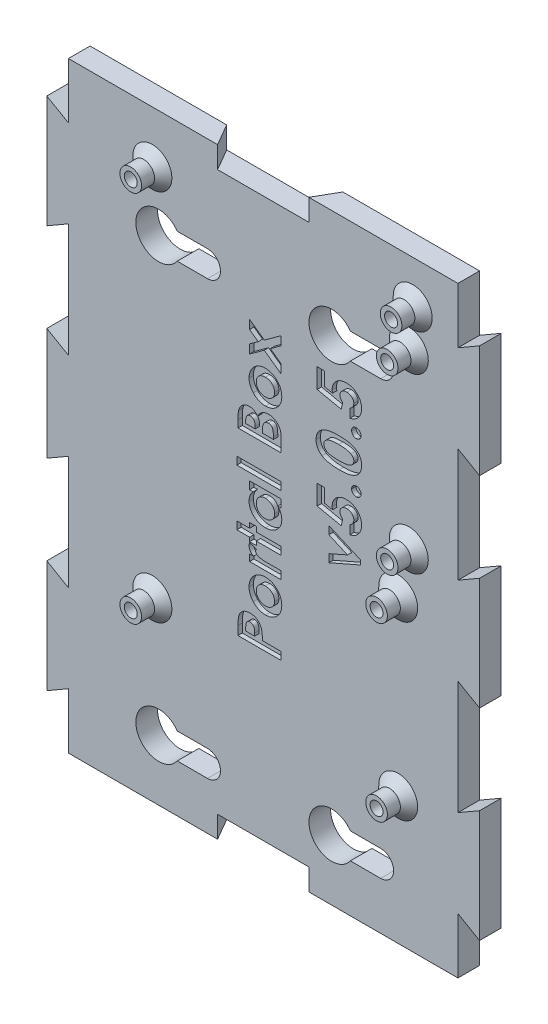
SolidWorks part; units mm, degrees
ref_plane "Front Plane" through (0, 0, 0) normal (1, 0, 0) x (0, 1, 0)
ref_plane "Top Plane" through (0, 0, 0) normal (0, 0, 1) x (0, 1, 0)
ref_plane "Right Plane" through (0, 0, 0) normal (0, 1, 0) x (-1, 0, 0)
sketch "Sketch2" plane through (0, 0, 0) normal (0, 0, 1) x (0, 1, 0)
  line L1 (-60.1282, -37.9423) -> (59.8718, -37.9423) construction
  line L2 (-60.1282, -37.9423) -> (-60.1282, 42.0577) construction
  line L3 (-60.1282, 42.0577) -> (59.8718, 42.0577) construction
  line L4 (59.8718, -37.9423) -> (59.8718, 42.0577) construction
  line L13 (-72.6282, 49.5577) -> (66.3718, 49.5577)
  line L14 (-72.6282, 49.5577) -> (-72.6282, -40.4423)
  line L15 (-72.6282, -40.4423) -> (66.3718, -40.4423)
  line L16 (66.3718, 49.5577) -> (66.3718, -40.4423)
  point P0 (0, 0)
  point P6 (0, 0)
  dimension "D1" = 120
  dimension "D2" = 80
  dimension "D3" = 12.5
  dimension "D5" = 139
  dimension "D6" = 90
  dimension "D7" = 7.5
extrude "Boss-Extrude1" add sketch "Sketch2" along normal blind 5
sketch "Sketch9" plane through (0, 0, 5) normal (0, 0, 1) x (1, 0, 0)
  line L0 (-0.3883, 34.4618) -> (-0.3883, -36.7916) construction
  text T0 "<b>Portal Box</b>\r\n<b> v5.0.5</b>" font "Century Gothic" height 10
extrude "Cut-Extrude4" cut sketch "Sketch9" against normal blind 1
sketch "Sketch12" plane through (0, 0, 5) normal (0, 0, 1) x (1, 0, 0)
  line L0 (-54.5577, 30.3911) -> (-54.5577, 56.3718)
  line L1 (-54.5577, 56.3718) -> (-32.0577, 43.3815)
  line L2 (-32.0577, 43.3815) -> (-54.5577, 30.3911)
  line L4 (-32.0577, -3.1282) -> (-54.5577, -16.1185)
  line L5 (-54.5577, -16.1185) -> (-54.5577, 9.8622)
  line L6 (-54.5577, 9.8622) -> (-32.0577, -3.1282)
  line L7 (-32.0577, -49.6378) -> (-54.5577, -62.6282)
  line L8 (-54.5577, -62.6282) -> (-54.5577, -36.6474)
  line L9 (-54.5577, -36.6474) -> (-32.0577, -49.6378)
  line L11 (0, 70.08) -> (0, -71.8273) construction
  line L12 (0, -55) -> (0, 55) construction
  line L22 (-49.5577, 66.3718) -> (-49.5577, -72.6282) construction
  line L23 (40.4423, 66.3718) -> (-49.5577, 66.3718) construction
  line L24 (-49.5577, -72.6282) -> (40.4423, -72.6282) construction
  line L26 (-4.5577, 66.3718) -> (-4.5577, -72.6282) construction
  line L28 (45.4423, 56.3718) -> (22.9423, 43.3815)
  line L29 (45.4423, 30.3911) -> (45.4423, 56.3718)
  line L30 (22.9423, 43.3815) -> (45.4423, 30.3911)
  line L31 (45.4423, 9.8622) -> (22.9423, -3.1282)
  line L32 (45.4423, -16.1185) -> (45.4423, 9.8622)
  line L33 (22.9423, -3.1282) -> (45.4423, -16.1185)
  line L34 (45.4423, -36.6474) -> (22.9423, -49.6378)
  line L35 (45.4423, -62.6282) -> (45.4423, -36.6474)
  line L36 (22.9423, -49.6378) -> (45.4423, -62.6282)
  circle A0 centre (-47.0577, 43.3815) radius 7.5
  dimension "D1" = 15
  dimension "D2" = 5
  dimension "D4" = 10
  dimension "D5" = 10
  dimension "D9" = 20.5289
  dimension "D10" = 20.5289
  dimension "D3" = 3
extrude "Boss-Extrude5" add sketch "Sketch12" against normal blind 5 contours L9 L8 L7 | L6 L5 L4 | A0 L0 L2 | A0 | A0 L1 L0 | A0 L2 L1 | L34 | L31 | L28 L30 L29 region at (-51.7998, 35.168, 5) region at (-51.7998, 51.5949, 5) region at (-47.0577, 43.3815, 5) region at (-37.5737, 43.3815, 5) region at (-47.0577, -3.1282, 5) region at (-47.0577, -49.6378, 5) region at (37.9423, -3.1282, 5) region at (37.9423, -49.6378, 5)
sketch "Sketch13" plane through (0, 66.3718, -60) normal (0, 1, 0) x (1, 0, 0)
  line L0 (-17.9811, -60) -> (8.8657, -60)
  line L1 (8.8657, -60) -> (-4.5577, -83.25)
  line L2 (-4.5577, -83.25) -> (-17.9811, -60)
  line L5 (40.4423, -65) -> (40.4423, -60) construction
  line L6 (-55, -60) -> (55, -60) construction
  circle A0 centre (-4.5577, -67.75) radius 7.75
  dimension "D1" = 15.5
  dimension "D2" = 0
  dimension "D3" = 45
extrude "Cut-Extrude5" cut sketch "Sketch13" along normal blind 5 from surface contours L1 L2 L0 starting at face at (-4.5577, -72.6282, 2.5)
extrude "Cut-Extrude6" cut sketch "Sketch13<3>" against normal blind 5 contours L0 L1 L2
sketch "Sketch13<3>" plane through (0, 66.3718, -60) normal (0, 1, 0) x (1, 0, 0) same geometry as "Sketch13"
sketch "Sketch11" plane through (0, 0, 5) normal (0, 0, 1) x (1, 0, 0)
  line L0 (-44.5577, 59.8718) -> (35.4423, 59.8718) construction
  line L1 (-44.5577, 59.8718) -> (-44.5577, -60.1282) construction
  line L2 (-44.5577, -60.1282) -> (35.4423, -60.1282) construction
  line L3 (35.4423, 59.8718) -> (35.4423, -60.1282) construction
  line L4 (-44.5577, 59.8718) -> (35.4423, -60.1282) construction
  line L5 (-44.5577, -60.1282) -> (35.4423, 59.8718) construction
  line L7 (-49.5577, -72.6282) -> (-15.0944, -72.6282) construction
  line L8 (-49.5577, -13.2318) -> (-49.5577, -39.5342) construction
  line L9 (40.4423, 53.4851) -> (40.4423, 66.3718) construction
  circle A0 centre (-30.1577, -31.8782) radius 2.5
  circle A1 centre (-30.1577, 54.3718) radius 2.5
  circle A2 centre (29.9923, 56.4218) radius 1.5
  circle A3 centre (29.9923, 56.4218) radius 2.5
  circle A4 centre (-30.1577, 54.3718) radius 1.5
  circle A5 centre (-30.1577, -31.8782) radius 1.5
  circle A6 centre (26.6423, -43.0782) radius 1.5
  circle A7 centre (26.6423, -3.3282) radius 1.5
  circle A8 centre (26.6423, -43.0782) radius 2.5
  circle A9 centre (26.6423, -3.3282) radius 2.5
  circle A10 centre (29.0923, 47.4718) radius 1.5
  circle A11 centre (29.0923, 7.5218) radius 1.5
  circle A12 centre (29.0923, 47.4718) radius 2.5
  circle A13 centre (29.0923, 7.5218) radius 2.5
  point P6 (0, 0)
  dimension "D5" = 3
  dimension "D6" = 5
  dimension "D8" = 5
  dimension "D9" = 3
  dimension "D11" = 5
  dimension "D12" = 3
  dimension "D17" = 3
  dimension "D18" = 3
  dimension "D19" = 5
  dimension "D20" = 5
  dimension "D25" = 3
  dimension "D26" = 3
  dimension "D27" = 5
  dimension "D28" = 5
  dimension "D1" = 80
  dimension "D2" = 120
  dimension "D3" = 3.45
  dimension "D4" = 5.45
  dimension "D7" = 14.4
  dimension "D10" = 28.25
  dimension "D13" = 17.05
  dimension "D14" = 8.8
  dimension "D15" = 56.8
  dimension "D16" = 8.8
  dimension "D21" = 6.35
  dimension "D22" = 6.35
  dimension "D23" = 52.35
  dimension "D24" = 12.4
  dimension "D29" = 14.4
  dimension "D30" = 5.5
  dimension "D31" = 12.5
  dimension "D32" = 5
  dimension "D33" = 5
extrude "Boss-Extrude4" add sketch "Sketch11" along normal blind 5
chamfer "Chamfer1" distance 2 angle 45 7 edges at (-27.6577, 54.3718, 5) (-27.6577, -31.8782, 5) (29.1423, -43.0782, 5) (29.1423, -3.3282, 5) (31.5923, 7.5218, 5) (31.5923, 47.4718, 5) (32.4923, 56.4218, 5)
sketch "Sketch14" plane through (0, 0, 0) normal (0, 0, -1) x (1, 0, 0)
  line L0 (22.5778, 61.6235) -> (15.5778, 61.6235)
  line L1 (22.5778, 55.6235) -> (15.5778, 55.6235)
  line L2 (22.5778, -38.3765) -> (15.5778, -38.3765)
  line L3 (22.5778, -44.3765) -> (15.5778, -44.3765)
  line L4 (-17.4222, 61.6235) -> (-24.4222, 61.6235)
  line L5 (-17.4222, 55.6235) -> (-24.4222, 55.6235)
  line L6 (-17.4222, -38.3765) -> (-24.4222, -38.3765)
  line L7 (-17.4222, -44.3765) -> (-24.4222, -44.3765)
  line L8 (15.5778, 55.6235) -> (15.5778, 61.6235)
  line L9 (22.5778, 61.6235) -> (22.5778, 55.6235)
  line L10 (-24.4222, 61.6235) -> (-24.4222, 55.6235)
  line L11 (-17.4222, 61.6235) -> (-17.4222, 55.6235)
  line L12 (-24.4222, -38.3765) -> (-24.4222, -44.3765)
  line L13 (-17.4222, -38.3765) -> (-17.4222, -44.3765)
  line L14 (15.5778, -38.3765) -> (15.5778, -44.3765)
  line L15 (22.5778, -38.3765) -> (22.5778, -44.3765)
  circle A2 centre (22.5778, 58.6235) radius 3
  circle A3 centre (22.5778, -41.3765) radius 3
  circle A4 centre (11.2694, 58.6235) radius 5.25
  circle A5 centre (11.2694, -41.3765) radius 5.25
  circle A6 centre (-17.4222, 58.6235) radius 3
  circle A7 centre (-17.4222, -41.3765) radius 3
  circle A8 centre (-28.7306, 58.6235) radius 5.25
  circle A9 centre (-28.7306, -41.3765) radius 5.25
  dimension "D1" = 6
  dimension "D2" = 10.5
  dimension "D3" = 10.5
  dimension "D4" = 6
  dimension "D5" = 10.5
  dimension "D6" = 10.5
  dimension "D7" = 7
  dimension "D8" = 7
  dimension "D9" = 7
  dimension "D10" = 7
  dimension "D11" = 7
  dimension "D12" = 7
  dimension "D13" = 7
  dimension "D14" = 7
  dimension "D15" = 40
  dimension "D16" = 100
extrude "Cut-Extrude7" cut sketch "Sketch14" against normal blind 10 contours A5 | L3 L14 L2 L15 | A3 | A9 | L7 L12 L6 L13 | A7 | A8 | L5 L10 L4 L11 | A6 | A4 | L1 L8 L0 L9 | A2
